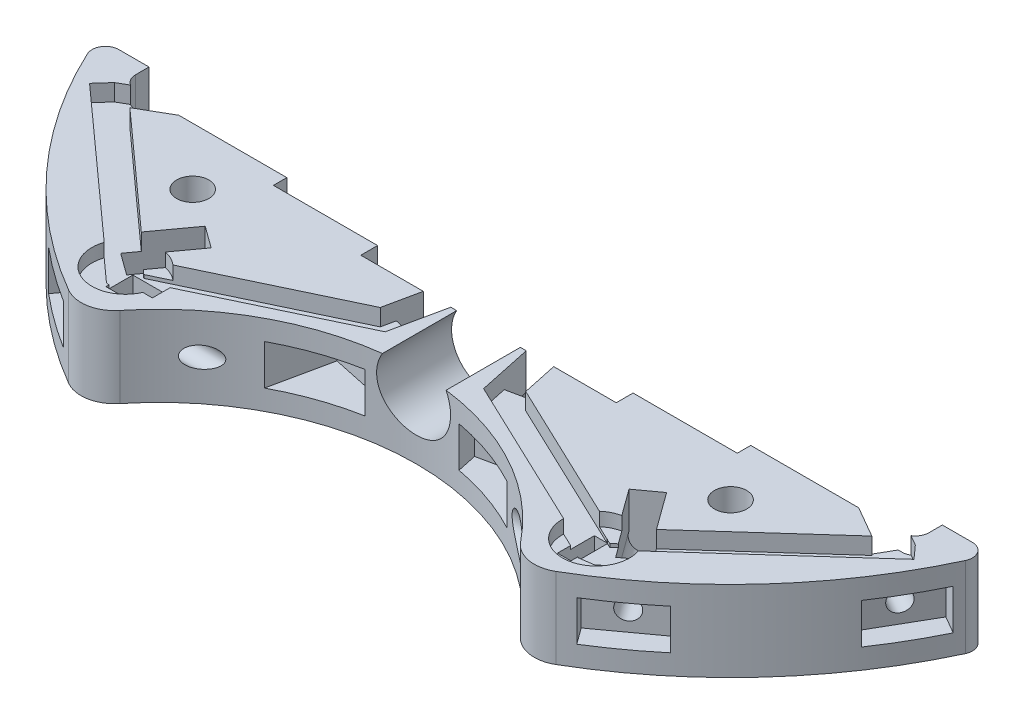
SolidWorks part; units mm, degrees
material "ABS"
ref_plane "Front Plane" through (0, 0, 0) normal (0, 0, 1) x (1, 0, 0)
ref_plane "Top Plane" through (0, 0, 0) normal (0, 1, 0) x (1, 0, 0)
ref_plane "Right Plane" through (0, 0, 0) normal (1, 0, 0) x (0, 0, -1)
sketch "Sketch1" plane through (0, 0, 0) normal (0, 1, 0) x (1, 0, 0)
  line L0 (0, -85) -> (-32.2211, -64.3879) construction
  line L1 (0, -85) -> (0, 0) construction
  arc A0 (36.2245, -62.2237) -> (-36.2245, -62.2237) centre (0, 0) ccw
  arc A1 (29.8119, -61.0352) -> (-29.8119, -61.0352) centre (0, -85) ccw
  arc A2 (36.2245, -62.2237) -> (29.8119, -61.0352) centre (33.7089, -57.9026) cw
  arc A3 (-29.8119, -61.0352) -> (-36.2245, -62.2237) centre (-33.7089, -57.9026) cw
  dimension "D1" = 144
  dimension "D2" = 76.5
  dimension "D4" = 5
  dimension "D3" = 85
extrude "Boss-Extrude1" add sketch "Sketch1" along normal mid plane 12
sketch "solenoid placement" plane through (0, 6, 0) normal (0, 1, 0) x (1, 0, 0)
  line L0 (0, 0) -> (0, -36) construction
  line L5 (-19, -36) -> (19, -36)
  line L7 (19, -36) -> (19, 28)
  line L9 (19, 28) -> (-19, 28)
  line L11 (-19, 28) -> (-19, -36)
  circle A1 centre (0, 0) radius 72 construction
  arc A2 (36.2245, -62.2237) -> (-36.2245, -62.2237) centre (0, 0) ccw construction
  point P7 (0, 28)
  dimension "D1" = 38
  dimension "D2" = 64
  dimension "D3" = 36
extrude "Cut-Extrude1" cut sketch "solenoid placement" against normal through all
sketch "Sketch6" plane through (0, 6, 0) normal (0, 1, 0) x (1, 0, 0)
  line L0 (0, 0) -> (0, -46.75) construction
  arc A0 (29.8119, -61.0352) -> (-29.8119, -61.0352) centre (0, -85) ccw construction
  circle A1 centre (40, -40) radius 2.4
  circle A4 centre (-40, -40) radius 2.4
  dimension "D1" = 4.8
  dimension "D2" = 40
  dimension "D3" = 40
extrude "Cut-Extrude6" cut sketch "Sketch6" against normal through all
sketch "Sketch3" plane through (0, 6, 0) normal (0, 1, 0) x (1, 0, 0)
  line L0 (-72, -27.5) -> (-59, -27.5)
  line L1 (-59, -31.5) -> (59, -31.5)
  line L2 (-72, -27.5) -> (-72, 31.5)
  line L3 (-59, -27.5) -> (-59, -31.5)
  line L4 (72, -27.5) -> (72, 31.5)
  line L5 (-72, 31.5) -> (72, 31.5) construction
  line L6 (0, 31.5) -> (0, -31.5) construction
  line L7 (59, -27.5) -> (59, -31.5)
  line L8 (-72, 31.5) -> (-72, 72)
  line L9 (72, -27.5) -> (59, -27.5)
  line L10 (-72, 72) -> (72, 72)
  line L11 (72, 31.5) -> (72, 72)
  arc A0 (36.2245, -62.2237) -> (-36.2245, -62.2237) centre (0, 0) ccw construction
  arc A1 (36.2245, -62.2237) -> (-36.2245, -62.2237) centre (0, 0) ccw construction
  point P0 (0, 0)
  dimension "D2" = 4
  dimension "D1" = 63
  dimension "D3" = 13
extrude "Cut-Extrude3" cut sketch "Sketch3" against normal through all
fillet "Fillet1" radius 2 4 edges at (66.5413, 0, 27.5) (59, 0, 31.5) (-66.5413, 0, 27.5) (-59, 0, 31.5)
sketch "Sketch8" plane through (0, 0, 0) normal (0, 1, 0) x (1, 0, 0)
  line L0 (0, 0) -> (62.3538, -36) construction
  line L1 (0, 0) -> (42.3205, -58.2492) construction
  line L2 (0, 0) -> (14.9696, -70.4266) construction
  line L3 (0, 0) -> (-14.9696, -70.4266) construction
  line L4 (-42.3205, -58.2492) -> (0, 0) construction
  line L5 (0, 0) -> (-62.3538, -36) construction
  line L6 (0, 0) -> (0, -72) construction
  arc A0 (-62.3538, -36) -> (-42.3205, -58.2492) centre (0, 0) ccw construction
  arc A1 (62.3538, -36) -> (42.3205, -58.2492) centre (0, 0) cw construction
  arc A2 (14.9696, -70.4266) -> (42.3205, -58.2492) centre (0, 0) ccw construction
  arc A3 (14.9696, -70.4266) -> (-14.9696, -70.4266) centre (0, 0) cw construction
  arc A4 (-14.9696, -70.4266) -> (-42.3205, -58.2492) centre (0, 0) cw construction
  arc A5 (36.2245, -62.2237) -> (65.294, -30.3429) centre (0, 0) ccw construction
  dimension "D1" = 120
sketch "Sketch9" plane through (0, 0, 0) normal (0, 1, 0) x (1, 0, 0)
  line L0 (0, 0) -> (-59.7033, -40.2432) construction
  line L1 (0, 0) -> (-64.7033, -31.583) construction
  line L2 (-64.7033, -31.583) -> (-59.7033, -40.2432) construction
  line L3 (-64.7033, -31.583) -> (-62.1052, -30.083)
  line L4 (-62.1052, -30.083) -> (-57.1052, -38.7432)
  line L5 (-57.1052, -38.7432) -> (-59.7033, -40.2432)
  line L6 (-46.2635, -55.1697) -> (-44.5001, -52.7426)
  line L7 (-44.5001, -52.7426) -> (-36.4099, -58.6205)
  line L8 (-36.4099, -58.6205) -> (-38.1733, -61.0475)
  line L9 (0, 0) -> (-38.1733, -61.0475) construction
  line L10 (0, 0) -> (-46.2635, -55.1697) construction
  line L11 (-46.2635, -55.1697) -> (-38.1733, -61.0475) construction
  line L12 (-19.8242, -69.217) -> (-19.2005, -66.2826) [skipped]
  line L13 (-19.2005, -66.2826) -> (-9.419, -68.3617) [skipped]
  line L14 (-9.419, -68.3617) -> (-10.0428, -71.2962) [skipped]
  line L15 (0, 0) -> (-10.0428, -71.2962) construction
  line L16 (0, 0) -> (-19.8242, -69.217) construction
  line L17 (-19.8242, -69.217) -> (-10.0428, -71.2962) construction
  line L18 (10.0428, -71.2962) -> (9.419, -68.3617) [skipped]
  line L19 (9.419, -68.3617) -> (19.2005, -66.2826) [skipped]
  line L20 (19.2005, -66.2826) -> (19.8242, -69.217) [skipped]
  line L21 (0, 0) -> (19.8242, -69.217) construction
  line L22 (0, 0) -> (10.0428, -71.2962) construction
  line L23 (10.0428, -71.2962) -> (19.8242, -69.217) construction
  line L24 (38.1733, -61.0475) -> (36.4099, -58.6205)
  line L25 (36.4099, -58.6205) -> (44.5001, -52.7426)
  line L26 (44.5001, -52.7426) -> (46.2635, -55.1697)
  line L27 (0, 0) -> (46.2635, -55.1697) construction
  line L28 (0, 0) -> (38.1733, -61.0475) construction
  line L29 (38.1733, -61.0475) -> (46.2635, -55.1697) construction
  line L30 (59.7033, -40.2432) -> (57.1052, -38.7432)
  line L31 (57.1052, -38.7432) -> (62.1052, -30.083)
  line L32 (62.1052, -30.083) -> (64.7033, -31.583)
  line L33 (0, 0) -> (64.7033, -31.583) construction
  line L34 (0, 0) -> (59.7033, -40.2432) construction
  line L35 (59.7033, -40.2432) -> (64.7033, -31.583) construction
  arc A0 (-59.7033, -40.2432) -> (-64.7033, -31.583) centre (0, 0) cw
  arc A1 (-62.3538, -36) -> (-42.3205, -58.2492) centre (0, 0) ccw construction
  arc A2 (-38.1733, -61.0475) -> (-46.2635, -55.1697) centre (0, 0) cw
  arc A3 (-10.0428, -71.2962) -> (-19.8242, -69.217) centre (0, 0) cw [skipped]
  arc A4 (19.8242, -69.217) -> (10.0428, -71.2962) centre (0, 0) cw [skipped]
  arc A5 (46.2635, -55.1697) -> (38.1733, -61.0475) centre (0, 0) cw
  arc A6 (64.7033, -31.583) -> (59.7033, -40.2432) centre (0, 0) cw
  point P8 (-62.3538, -36)
  point P12 (62.3538, -36)
  point P34 (0, 0)
  dimension "D1" = 10
  dimension "D2" = 3
  dimension "D3" = 6
extrude "Cut-Extrude7" cut sketch "Sketch9" against normal mid plane 6
sketch "Sketch11" plane through (0, 0, 36) normal (0, 0, -1) x (-1, 0, 0)
  line L0 (0, -6) -> (0, 3.2) construction
  line L1 (19, -6) -> (-19, -6) construction
  circle A0 centre (0, 3.2) radius 5.5
  dimension "D2" = 11
  dimension "D1" = 9.2
extrude "Cut-Extrude8" cut sketch "Sketch11" against normal through all
sketch "Sketch12" plane through (0, 6, 0) normal (0, 1, 0) x (1, 0, 0)
  line L1 (-34.5, 33.5) -> (34.5, 33.5)
  line L2 (-34.5, 33.5) -> (-34.5, -33.5)
  line L3 (-34.5, -33.5) -> (34.5, -33.5)
  line L4 (34.5, 33.5) -> (34.5, -33.5)
  line L5 (-34.5, 33.5) -> (34.5, -33.5) construction
  line L6 (-34.5, -33.5) -> (34.5, 33.5) construction
  point P0 (0, 0)
  dimension "D1" = 69
  dimension "D2" = 67
extrude "Cut-Extrude9" cut sketch "Sketch12" against normal through all
sketch "Sketch13" plane through (0, 6, 0) normal (0, 1, 0) x (1, 0, 0)
  line L0 (0, 0) -> (0, -97.3817) construction
  circle A0 centre (-35, -55) radius 5
  circle A1 centre (35, -55) radius 5
  dimension "D3" = 10
  dimension "D1" = 35
  dimension "D2" = 55
extrude "Cut-Extrude10" cut sketch "Sketch13" against normal blind 2
sketch "Sketch14" plane through (0, 0, 0) normal (0, 1, 0) x (1, 0, 0)
  line L0 (16.1653, -42.3838) -> (6.3839, -44.463)
  line L1 (16.1653, -42.3838) -> (16.7891, -45.3183)
  line L2 (6.3839, -44.463) -> (7.0076, -47.3974)
  line L3 (16.7891, -45.3183) -> (7.0076, -47.3974) construction
  line L4 (0, 0) -> (14.9696, -70.4266) construction
  line L5 (16.7891, -45.3183) -> (7.0076, -47.3974) construction
  line L6 (16.7891, -45.3183) -> (18.0563, -51.2801)
  line L7 (7.0076, -47.3974) -> (8.2748, -53.3592)
  line L8 (18.0563, -51.2801) -> (8.2748, -53.3592)
  line L9 (0, 0) -> (0, -72) construction
  line L10 (-16.7891, -45.3183) -> (-7.0076, -47.3974) construction
  line L11 (-16.7891, -45.3183) -> (-7.0076, -47.3974) construction
  line L12 (-18.0563, -51.2801) -> (-8.2748, -53.3592)
  line L13 (-7.0076, -47.3974) -> (-8.2748, -53.3592)
  line L14 (-16.7891, -45.3183) -> (-18.0563, -51.2801)
  line L15 (-6.3839, -44.463) -> (-7.0076, -47.3974)
  line L16 (-16.1653, -42.3838) -> (-16.7891, -45.3183)
  line L17 (-16.1653, -42.3838) -> (-6.3839, -44.463)
  arc A0 (29.8119, -61.0352) -> (4.7339, -47.0441) centre (0, -85) ccw construction
  dimension "D1" = 10
  dimension "D2" = 3
  dimension "D3" = 3
extrude "Cut-Extrude11" cut sketch "Sketch14" against normal mid plane 6
sketch "Sketch15" plane through (59.6052, 0, 34.4131) normal (0.866, 0, 0.5) x (0.5, 0, -0.866)
  circle A0 centre (0, 0) radius 1.55
  dimension "D1" = 3.1
extrude "Cut-Extrude12" cut sketch "Sketch15" against normal blind 4.2
sketch "Sketch16" plane through (55.9679, 0, 32.3131) normal (0.866, 0, 0.5) x (0.5, 0, -0.866)
  circle A0 centre (0, 0) radius 2.1
  dimension "D1" = 4.2
extrude "Cut-Extrude13" cut sketch "Sketch16" against normal blind 9
sketch "Sketch17" plane through (55.9679, 0, 32.3131) normal (-0.866, 0, -0.5) x (-0.5, 0, 0.866)
  line L1 (-2, 0) -> (2, 0)
  line L2 (-2, 0) -> (-2, 7.9151)
  line L3 (-2, 7.9151) -> (2, 7.9151)
  line L4 (2, 0) -> (2, 7.9151)
  point P0 (0, 0)
  dimension "D1" = 4
extrude "Cut-Extrude14" cut sketch "Sketch17" along normal blind 9
pattern_circular "CirPattern1" count 6 over 120 about axis through (0, 6, 0) along (0, -1, 0) of "Cut-Extrude12", "Cut-Extrude13", "Cut-Extrude14"
sketch "Sketch18" plane through (9.3183, 0, 43.8392) normal (0.2079, 0, 0.9781) x (0.9781, 0, -0.2079)
  circle A0 centre (0, 0) radius 1.55
  dimension "D1" = 3.1
extrude "Cut-Extrude15" cut sketch "Sketch18" against normal blind 4.2
sketch "Sketch19" plane through (8.4451, 0, 39.731) normal (0.2079, 0, 0.9781) x (0.9781, 0, -0.2079)
  circle A0 centre (0, 0) radius 2.1
  dimension "D1" = 4.2
extrude "Cut-Extrude16" cut sketch "Sketch19" against normal blind 9
sketch "Sketch20" plane through (8.4451, 0, 39.731) normal (-0.2079, 0, -0.9781) x (-0.9781, 0, 0.2079)
  line L1 (-2, 0) -> (2, 0)
  line L2 (-2, 0) -> (-2, 10.352)
  line L3 (-2, 10.352) -> (2, 10.352)
  line L4 (2, 0) -> (2, 10.352)
  point P0 (0, 0)
  dimension "D1" = 4
extrude "Cut-Extrude17" cut sketch "Sketch20" along normal blind 9
pattern_circular "CirPattern2" count 2 over 24 about axis through (0, 6, 0) along (0, -1, 0) of "Cut-Extrude15", "Cut-Extrude16", "Cut-Extrude17"
sketch "Sketch21" plane through (0, 6, 0) normal (0, 1, 0) x (1, 0, 0)
  line L0 (10.4014, -39.3152) -> (6.4888, -40.1468)
  line L1 (6.4888, -40.1468) -> (7.1125, -43.0813)
  line L2 (7.1125, -43.0813) -> (11.0251, -42.2496) construction
  line L3 (10.8198, -41.2836) -> (10.4014, -39.3152)
  line L4 (35, -55) -> (58.566, -33.8131) construction
  line L5 (54.9679, -34.0451) -> (56.9679, -30.581)
  line L6 (56.9679, -30.581) -> (59.566, -32.081)
  line L8 (55.1801, -34.1677) -> (54.9679, -34.0451)
  line L10 (59.566, -32.081) -> (57.566, -35.5451) construction
  line L11 (56.4374, -31.5) -> (54.9679, -34.0451) construction
  line L12 (0, 0) -> (62.3538, -36) construction
  line L13 (9.0688, -42.6654) -> (35, -55) construction
  line L14 (36.3371, -56.4873) -> (61.3173, -34.029)
  line L15 (34.6547, -52.621) -> (55.1801, -34.1677)
  line L16 (7.3179, -44.0473) -> (34.1409, -56.8061)
  line L17 (10.8198, -41.2836) -> (34.6547, -52.621)
  line L18 (61.3173, -34.029) -> (59.566, -32.081)
  line L19 (7.3179, -44.0473) -> (7.1125, -43.0813)
  line L20 (36.3371, -56.4873) -> (34.1409, -56.8061)
  line L21 (33.6629, -53.5127) -> (58.643, -31.0544) construction
  line L22 (9.036, -40.4351) -> (35.8591, -53.1939) construction
  line L23 (11.0251, -42.2496) -> (10.8198, -41.2836) construction
  line L24 (8.177, -42.2412) -> (35, -55) construction
  line L25 (57.566, -35.5451) -> (55.1801, -34.1677) construction
  line L26 (35, -55) -> (59.9801, -32.5417) construction
  line L27 (0, 0) -> (0, -87.81) construction
  line L28 (-57.566, -35.5451) -> (-55.1801, -34.1677) construction
  line L29 (-11.0251, -42.2496) -> (-10.8198, -41.2836) construction
  line L30 (-9.0688, -42.6654) -> (-35, -55) construction
  line L31 (-59.566, -32.081) -> (-57.566, -35.5451) construction
  line L32 (-35, -55) -> (-58.566, -33.8131) construction
  line L33 (-7.1125, -43.0813) -> (-11.0251, -42.2496) construction
  line L34 (-36.3371, -56.4873) -> (-34.1409, -56.8061)
  line L35 (-7.3179, -44.0473) -> (-7.1125, -43.0813)
  line L36 (-61.3173, -34.029) -> (-59.566, -32.081)
  line L37 (-10.8198, -41.2836) -> (-34.6547, -52.621)
  line L38 (-7.3179, -44.0473) -> (-34.1409, -56.8061)
  line L39 (-34.6547, -52.621) -> (-55.1801, -34.1677)
  line L40 (-36.3371, -56.4873) -> (-61.3173, -34.029)
  line L41 (-55.1801, -34.1677) -> (-54.9679, -34.0451)
  line L42 (-56.9679, -30.581) -> (-59.566, -32.081)
  line L43 (-54.9679, -34.0451) -> (-56.9679, -30.581)
  line L44 (-10.8198, -41.2836) -> (-10.4014, -39.3152)
  line L45 (-6.4888, -40.1468) -> (-7.1125, -43.0813)
  line L46 (-10.4014, -39.3152) -> (-6.4888, -40.1468)
  point P22 (55.9679, -32.3131)
  dimension "D1" = 3
  dimension "D2" = 2
  dimension "D3" = 2
  dimension "D4" = 2
  dimension "D5" = 2
extrude "Cut-Extrude19" cut sketch "Sketch21" against normal blind 2.5
sketch "Sketch22" plane through (0, 0, 0) normal (1, 0, 0) x (0, 0, -1)
  line L0 (-55, 0) -> (0, 0) construction
  circle A0 centre (-55, 0) radius 1.55
  dimension "D1" = 3.1
  dimension "D2" = 55
extrude "Cut-Extrude20" cut sketch "Sketch22" against normal blind 29
sketch "Sketch23" plane through (-29, 0, 0) normal (1, 0, 0) x (0, 0, -1)
  line L0 (-55, 0) -> (-55, 8.7926) construction
  line L1 (-57, 8.7926) -> (-53, 8.7926)
  line L2 (-57, 8.7926) -> (-57, 0.6403)
  line L4 (-53, 8.7926) -> (-53, 0.6403)
  arc A0 (-57, 0.6403) -> (-53, 0.6403) centre (-55, 0) ccw
  dimension "D1" = 4.2
  dimension "D2" = 4
extrude "Cut-Extrude21" cut sketch "Sketch23" against normal blind 6.9
sketch "Sketch24" plane through (0, 0, 0) normal (1, 0, 0) x (0, 0, -1)
  circle A0 centre (-55, 0) radius 2.75
  circle A1 centre (-55, 0) radius 1.55 construction
  dimension "D1" = 5.5
extrude "Cut-Extrude23" cut sketch "Sketch24" along normal blind 30
sketch "Sketch25" plane through (30, 0, 0) normal (-1, 0, 0) x (0, 0, 1)
  line L1 (52.25, 0.5) -> (57.75, 0.5)
  line L2 (52.25, 0.5) -> (52.25, -0.5)
  line L3 (52.25, -0.5) -> (57.75, -0.5)
  line L4 (57.75, 0.5) -> (57.75, -0.5)
  line L5 (52.25, 0.5) -> (57.75, -0.5) construction
  line L6 (52.25, -0.5) -> (57.75, 0.5) construction
  circle A0 centre (55, 0) radius 2.75 construction
  point P0 (55, 0)
  dimension "D1" = 1
extrude "Cut-Extrude24" cut sketch "Sketch25" against normal blind 4
sketch "Sketch26" plane through (0, 0.5, 0) normal (0, -1, 0) x (1, 0, 0)
  line L1 (34, 52.25) -> (32, 52.25)
  line L2 (34, 52.25) -> (34, 57.75)
  line L3 (34, 57.75) -> (32, 57.75)
  line L4 (32, 52.25) -> (32, 57.75)
  point P4 (33.6435, 52.3916)
  point P5 (0, 0)
  dimension "D1" = 2
extrude "Cut-Extrude25" cut sketch "Sketch26" against normal through all
equation "\"smallPulleyTeeth\"= 30"
equation "\"largePulleyTeeth\"= 30"
equation "\"eighthThick\"= 3.0mm"
equation "\"sixteenthThick\" = 1.7mm"
equation "\"quarterThick\"=6.0mm"
equation "\"OD\" = 145mm"
equation "\"puckAngle\" = 60.5deg"
equation "\"puckDiam\" = 76.5mm"
equation "\"D2@Sketch1\"=\"puckDiam\""
equation "\"D1@Boss-Extrude1\"=\"eighthThick\"*4"
equation "\"axlePress\" = 5.9mm"
equation "\"press\" = 0.2mm"
equation "\"wheelClear\" = 0.3mm"
equation "\"10-32clear\" = 4.8mm"
equation "\"6-32clear\" = 3.3mm"
equation "\"8-32clear\" = 4.0mm"
equation "\"wheelHeight\" = 22mm"
equation "\"wheelWell\" = 65mm"
equation "\"puckDist\" = 85mm"
equation "\"scoopFillet\" = 5mm"
equation "\"4-40clear\" = 3.0mm"
equation "\"D3@Sketch1\"=\"puckDist\""
equation "\"D4@Sketch1\"=\"scoopFillet\""
equation "\"D1@Sketch6\"=\"10-32clear\""
equation "\"D2@Sketch9\"=\"eighthThick\""
equation "\"D2@Sketch14\"=\"eighthThick\""
equation "\"10-32tap\" = 4.45mm"
equation "\"ledSmall\" = 3.1mm"
equation "\"ledLarge\" = 4.2mm"
equation "\"ledLength\" = 4.2mm"
equation "\"D1@Cut-Extrude12\"=\"ledLength\""
equation "\"D1@Sketch15\"=\"ledSmall\""
equation "\"D1@Sketch16\"=\"ledLarge\""
equation "\"D1@Sketch18\"=\"ledSmall\""
equation "\"D1@Cut-Extrude15\"=\"ledLength\""
equation "\"D1@Sketch19\"=\"ledLarge\""
equation "\"D1@Sketch23\"=\"ledLarge\""
